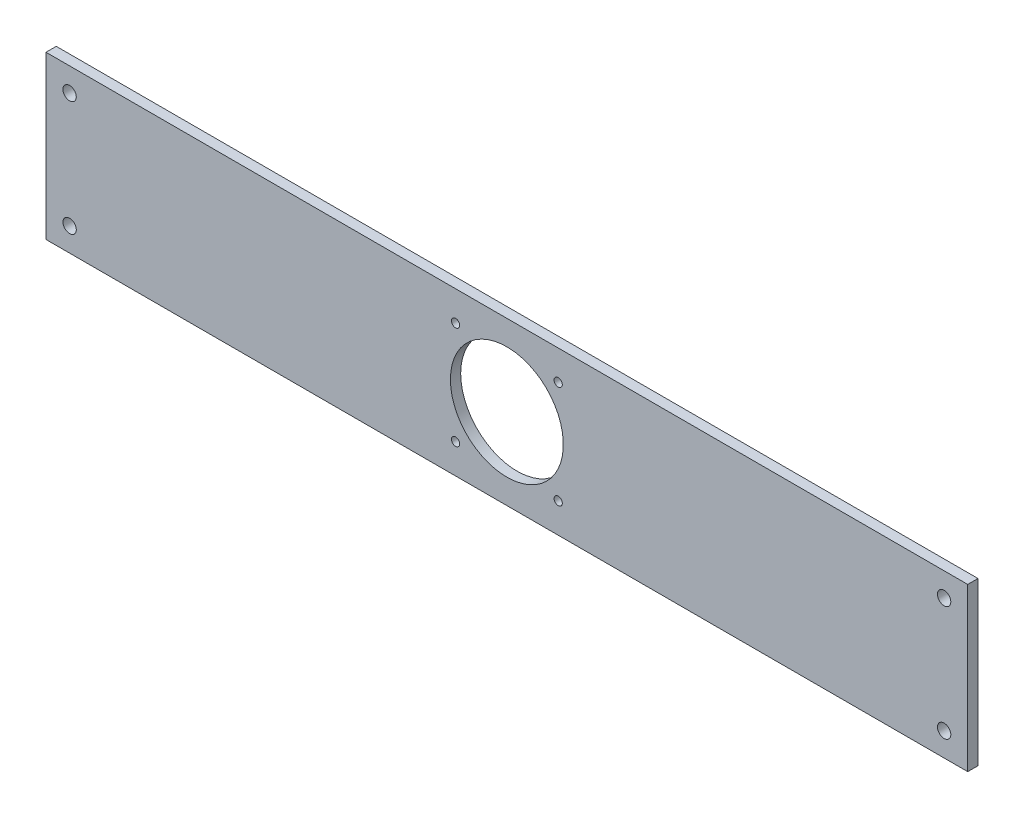
SolidWorks part; units mm, degrees
ref_plane "Piano frontale" through (0, 0, 0) normal (0, 0, 1) x (1, 0, 0)
ref_plane "Piano superiore" through (0, 0, 0) normal (0, 1, 0) x (1, 0, 0)
ref_plane "Piano destro" through (0, 0, 0) normal (1, 0, 0) x (0, 0, -1)
sketch "f" plane through (0, 0, 0) normal (0, 0, 1) x (1, 0, 0)
  line L0 (0, 0) -> (0, 79)
  line L1 (0, 79) -> (449, 79)
  line L2 (449, 79) -> (449, 0)
  line L3 (449, 0) -> (0, 0)
  line L4 (0, 39.5) -> (449, 39.5) construction
  line L5 (224.5, 42) -> (224.5, 123.488) construction
  line L10 (449, 79) -> (224.5, 0) construction
  line L11 (334, 39.5) -> (334, 81.5) construction
  line L12 (224.5, 0) -> (0, 79) construction
  line L13 (112.25, 42) -> (112.25, 84) construction
  circle A0 centre (11.5, 67.5) radius 3.25
  circle A1 centre (437.5, 67.5) radius 3.25
  circle A2 centre (11.5, 11.5) radius 3.25
  circle A3 centre (437.5, 11.5) radius 3.25
  dimension "D3" = 11.5
  dimension "D4" = 11.5
  dimension "D5" = 6.5
  dimension "D1" = 79
  dimension "D2" = 449
extrude "Estrusione-Estrusione1" add sketch "f" along normal blind 5
sketch "Sketch1" plane through (0, 0, 0) normal (0, 0, -1) x (-1, 0, 0)
  line L0 (-224.5, 79) -> (-224.5, 0) construction
  line L1 (-449, 79) -> (0, 79) construction
  line L2 (0, 0) -> (-449, 0) construction
  line L3 (0, 39.5) -> (-449, 39.5) construction
  line L4 (0, 79) -> (0, 0) construction
  line L5 (-449, 0) -> (-449, 79) construction
  point P12 (-249.5, 64.5)
  point P13 (-199.5, 64.5)
  point P14 (-199.5, 14.5)
  point P15 (-249.5, 14.5)
  dimension "D1" = 25
  dimension "D2" = 25
hole_wizard "Ø4.0 (4) Diameter Hole1" positions "Sketch4" profile "Sketch3" hole size "Ø4.0" standard "ISO" end condition through all
sketch "Sketch4" plane through (0, 0, 0) normal (0, 0, -1) x (-1, 0, 0)
  point P0 (-249.5, 64.5)
  point P3 (-199.5, 64.5)
  point P6 (-249.5, 14.5)
  point P9 (-199.5, 14.5)
sketch "Sketch3" plane through (249.5, 64.5, 0) normal (1, 0, 0) x (0, 1, 0)
  line L0 (0, 0) -> (0, 5)
  line L1 (0, 5) -> (2, 5)
  line L2 (2, 5) -> (2, 0)
  line L5 (2, 0) -> (0, 0)
  line L11 (0, -6.35) -> (0, 107.95) construction
  dimension "Thru Hole Dia." = 4
  dimension "Thru Hole Depth" = 5
sketch "Sketch5" plane through (0, 0, 0) normal (0, 0, -1) x (-1, 0, 0)
  line L0 (0, 39.5) -> (-449, 39.5) construction
  circle A0 centre (-224.5, 39.5) radius 27.5
  dimension "D1" = 55
extrude "Cut-Extrude1" cut sketch "Sketch5" against normal through all
